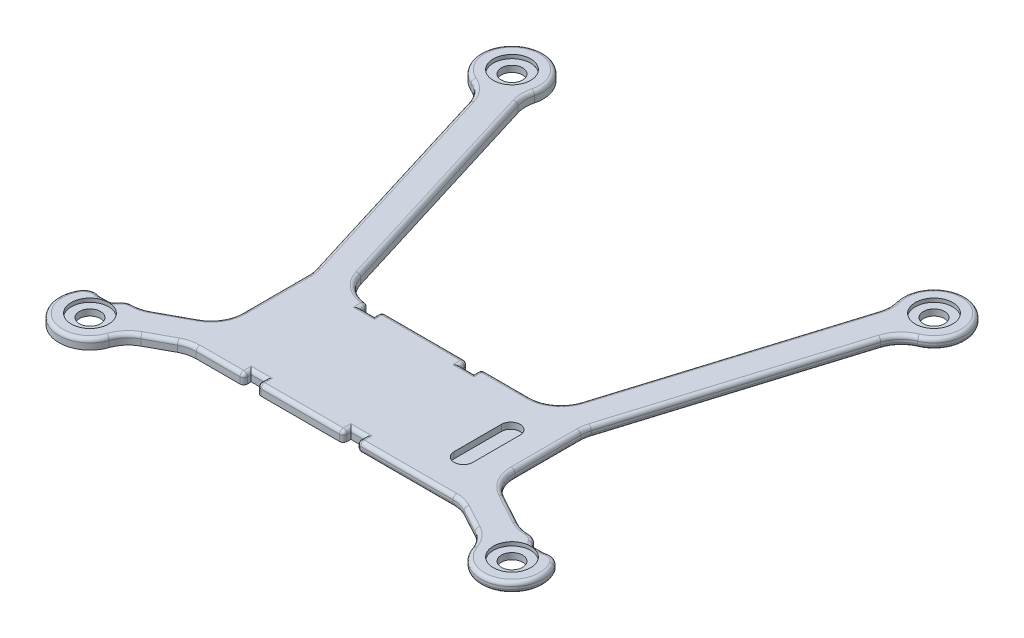
SolidWorks part; units mm, degrees
note: The reader was unsure of these and kept them because the rebuilt part matched: shared geometry of "草图1<4>".
material "PETG"
ref_plane "前视基准面" through (0, 0, 0) normal (0, 0, 1) x (1, 0, 0)
ref_plane "上视基准面" through (0, 0, 0) normal (0, 1, 0) x (1, 0, 0)
ref_plane "右视基准面" through (0, 0, 0) normal (1, 0, 0) x (0, 0, -1)
other "Configuration Table"
sketch "草图1" plane through (0, 0, 0) normal (0, 1, 0) x (1, 0, 0)
  line L0 (0, 38.1) -> (0, -38.1) construction
  line L1 (-33.9, -33.9) -> (33.9, -33.9) construction
  line L2 (-33.9, -33.9) -> (-33.9, 33.9) construction
  line L3 (-33.9, 33.9) -> (33.9, 33.9) construction
  line L4 (33.9, -33.9) -> (33.9, 33.9) construction
  line L5 (-33.9, -33.9) -> (33.9, 33.9) construction
  line L6 (-33.9, 33.9) -> (33.9, -33.9) construction
  line L7 (-21.9, -10.1) -> (21.9, -10.1)
  line L8 (-21.9, -10.1) -> (-21.9, -30.1)
  line L9 (-21.9, -30.1) -> (21.9, -30.1)
  line L10 (21.9, -10.1) -> (21.9, -30.1)
  line L11 (-21.9, -10.1) -> (21.9, -30.1) construction
  line L12 (-21.9, -30.1) -> (21.9, -10.1) construction
  line L13 (-38.1, 38.1) -> (38.1, 38.1) construction
  line L14 (-38.1, 38.1) -> (-38.1, -38.1) construction
  line L15 (-38.1, -38.1) -> (38.1, -38.1) construction
  line L16 (38.1, 38.1) -> (38.1, -38.1) construction
  line L17 (-38.1, 38.1) -> (38.1, -38.1) construction
  line L18 (-38.1, -38.1) -> (38.1, 38.1) construction
  line L19 (-21.9, -30.1) -> (-28.9, -33.9)
  line L20 (21.9, -30.1) -> (28.9, -33.9)
  line L21 (-31.4018, -29.5689) -> (-21.9, -24.4108)
  line L22 (31.4018, -29.5689) -> (21.9, -24.4108)
  line L23 (-33.9, 28.9) -> (-21.9, -10.1)
  line L24 (33.9, 28.9) -> (21.9, -10.1)
  line L25 (-29.485, 31.5531) -> (-16.6687, -10.1)
  line L26 (29.485, 31.5531) -> (16.6687, -10.1)
  circle A0 centre (-33.9, 33.9) radius 1.7
  circle A1 centre (33.9, 33.9) radius 1.7
  circle A2 centre (-33.9, -33.9) radius 1.7
  circle A3 centre (33.9, -33.9) radius 1.7
  circle A4 centre (-33.9, 33.9) radius 5
  circle A5 centre (33.9, 33.9) radius 5
  circle A6 centre (33.9, -33.9) radius 5
  circle A7 centre (-33.9, -33.9) radius 5
  circle A8 centre (-33.9, 33.9) radius 3
  circle A9 centre (33.9, 33.9) radius 3
  circle A10 centre (33.9, -33.9) radius 3
  circle A11 centre (-33.9, -33.9) radius 3
  point P0 (0, 0)
  point P14 (0, -20.1)
  point P19 (0, 0)
  dimension "D2" = 3.4
  dimension "D3" = 10
  dimension "D10" = 6
  dimension "D1" = 67.8
  dimension "D4" = 5
  dimension "D5" = 20
  dimension "D6" = 76.2
  dimension "D7" = 8
  dimension "D8" = 12
  dimension "D9" = 5
extrude "凸台-拉伸1" add sketch "草图1" along normal blind 1.6 contours A4 L23 L7 L25 | A5 L26 L7 L24 | L10 L7 L8 L9 | A6 L22 L10 L20 | A6 A10 | A10 A3 | A5 A9 | A9 A1 | A7 A11 | A7 L19 L8 L21 | A11 A2 | A4 A8 | A8 A0
extrude "切除-拉伸1" cut sketch "草图1<4>" against normal blind 0.6 from surface at 1.6 contours A8 A0 | A11 A2 | A10 A3 | A9 A1 starting at face at (0, 1.6, 9.3042)
sketch "草图1<4>" plane through (0, 0, 0) normal (0, 1, 0) x (1, 0, 0) same geometry as "草图1"
sketch "草图2" plane through (0, 1.6, 0) normal (0, 1, 0) x (1, 0, 0)
  line L0 (0, 0) -> (0, -30.1) construction
  line L2 (-33.9, -33.9) -> (-33.9, 33.9) construction
  line L3 (-21.9, -30.1) -> (21.9, -30.1) construction
  line L4 (-34.95, -33.9) -> (-34.95, -22.25) construction
  line L5 (36.6, -30.5) -> (33.3, -14) construction
  line L7 (-35.6, -14) -> (-34.3, -14)
  line L8 (-36.6, -15) -> (-36.6, -29.5)
  line L9 (-35.6, -30.5) -> (-34.3, -30.5)
  line L10 (-33.3, -15) -> (-33.3, -29.5)
  line L11 (-36.6, -14) -> (-33.3, -30.5) construction
  line L12 (-36.6, -30.5) -> (-33.3, -14) construction
  line L13 (36.6, -14) -> (33.3, -30.5) construction
  line L14 (34.95, -33.9) -> (34.95, -22.25) construction
  line L18 (33.3, -15) -> (33.3, -29.5)
  line L19 (35.6, -30.5) -> (34.3, -30.5)
  line L20 (36.6, -15) -> (36.6, -29.5)
  line L21 (35.6, -14) -> (34.3, -14)
  line L22 (-11.9, -10.1) -> (-11.9, -30.1) construction
  line L23 (-16.6687, -10.1) -> (16.6687, -10.1) construction
  line L24 (4.1, -10.1) -> (4.1, -30.1) construction
  line L25 (-11.9, -20.1) -> (4.1, -20.1) construction
  line L26 (-21.9, -10.1) -> (-21.9, -24.4108) construction
  line L27 (-13, -31.3) -> (-10.8, -31.3)
  line L28 (-13, -11.3) -> (-10.8, -11.3)
  line L29 (-13, -11.3) -> (-13, -8.9)
  line L30 (-13, -8.9) -> (-10.8, -8.9)
  line L31 (-10.8, -11.3) -> (-10.8, -8.9)
  line L32 (-13, -11.3) -> (-10.8, -8.9) construction
  line L33 (-13, -8.9) -> (-10.8, -11.3) construction
  line L34 (3, -11.3) -> (5.2, -11.3)
  line L35 (3, -11.3) -> (3, -8.9)
  line L36 (3, -8.9) -> (5.2, -8.9)
  line L37 (5.2, -11.3) -> (5.2, -8.9)
  line L38 (3, -11.3) -> (5.2, -8.9) construction
  line L39 (3, -8.9) -> (5.2, -11.3) construction
  line L40 (-10.8, -28.9) -> (-10.8, -31.3)
  line L41 (-13, -28.9) -> (-10.8, -28.9)
  line L42 (-13, -28.9) -> (-13, -31.3)
  line L43 (3, -31.3) -> (5.2, -31.3)
  line L44 (5.2, -28.9) -> (5.2, -31.3)
  line L45 (3, -28.9) -> (5.2, -28.9)
  line L46 (3, -28.9) -> (3, -31.3)
  arc A0 (-34.3, -30.5) -> (-33.3, -29.5) centre (-34.3, -29.5) ccw
  arc A1 (-36.6, -29.5) -> (-35.6, -30.5) centre (-35.6, -29.5) ccw
  arc A2 (-35.6, -14) -> (-36.6, -15) centre (-35.6, -15) ccw
  arc A3 (-34.3, -14) -> (-33.3, -15) centre (-34.3, -15) cw
  arc A4 (34.3, -14) -> (33.3, -15) centre (34.3, -15) ccw
  arc A5 (35.6, -14) -> (36.6, -15) centre (35.6, -15) cw
  arc A6 (36.6, -29.5) -> (35.6, -30.5) centre (35.6, -29.5) cw
  arc A7 (34.3, -30.5) -> (33.3, -29.5) centre (34.3, -29.5) cw
  dimension "D3" = 1
  dimension "D1" = 1.05
  dimension "D2" = 3.3
  dimension "D4" = 3.4
  dimension "D5" = 16.5
  dimension "D6" = 10
  dimension "D7" = 16
  dimension "D8" = 2.2
  dimension "D9" = 1.2
extrude "切除-拉伸2" cut sketch "草图2" against normal through all
fillet "圆角1" radius 5 16 edges at (-16.6687, 0.8, 10.1) (16.6687, 0.8, 10.1) (29.485, 0.8, -31.5531) (33.9, 0.8, -28.9) (21.9, 0.8, 10.1) (21.9, 0.8, 24.4108) (31.4018, 0.8, 29.5689) (28.9, 0.8, 33.9) (21.9, 0.8, 30.1) (-31.4018, 0.8, 29.5689) (-21.9, 0.8, 24.4108) (-21.9, 0.8, 10.1) (-33.9, 0.8, -28.9) (-29.485, 0.8, -31.5531) (-21.9, 0.8, 30.1) (-28.9, 0.8, 33.9)
fillet "圆角2" radius 2 4 edges at (-33.3, 0.8, 28.9361) (36.5835, 0.8, 29.6811) (-36.5835, 0.8, 29.6811) (33.3, 0.8, 28.9361)
fillet "圆角3" radius 0.6 8 edges at (5.2, 0.8, 10.1) (3, 0.8, 10.1) (-13, 0.8, 10.1) (-10.8, 0.8, 10.1) (5.2, 0.8, 30.1) (3, 0.8, 30.1) (-10.8, 0.8, 30.1) (-13, 0.8, 30.1)
sketch "草图4" plane through (0, 1.6, 0) normal (0, 1, 0) x (1, 0, 0)
  line L0 (16.1, -16.3) -> (16.1, -23.9) construction
  line L1 (17.6, -16.3) -> (17.6, -23.9)
  line L2 (14.6, -16.3) -> (14.6, -23.9)
  line L3 (-21.9, -10.8518) -> (-21.9, -21.4358) construction
  line L4 (-21.9, -20.1) -> (21.9, -20.1) construction
  line L5 (21.9, -10.8518) -> (21.9, -21.4358) construction
  line L6 (-10.2, -10.1) -> (2.4, -10.1) construction
  line L7 (-10.2, -30.1) -> (2.4, -30.1) construction
  arc A0 (17.6, -16.3) -> (14.6, -16.3) centre (16.1, -16.3) ccw
  arc A1 (14.6, -23.9) -> (17.6, -23.9) centre (16.1, -23.9) ccw
  point P2 (16.1, -20.1)
  point P18 (16.1, -25.4)
  dimension "D1" = 1.5
  dimension "D2" = 38
  dimension "D3" = 10.6
extrude "切除-拉伸3" cut sketch "草图4" against normal blind 1
fillet "圆角4" radius 0.6 91 edges at (5.2, 0, 29.2) (5.2, 1.6, 29.2) (5.3757, 1.6, 29.9243) (5.3757, 0, 29.9243) (13.2152, 1.6, 30.1) (13.2152, 0, 30.1) (21.8609, 1.6, 30.2538) (21.8609, 0, 30.2538) (24.9262, 0, 31.7428) (24.9262, 1.6, 31.7428) (28.2641, 1.6, 33.9397) (28.2641, 0, 33.9397) (5.2, 1.6, 11) (5.2, 0, 11) (5.3757, 1.6, 10.2757) (5.3757, 0, 10.2757) (9.3879, 0, 10.1) (9.3879, 1.6, 10.1) (15.9463, 1.6, 9.1219) (15.9463, 0, 9.1219) (23.3731, 0, -11.6893) (23.3731, 1.6, -11.6893) (29.2111, 1.6, -31.2999) (29.2111, 0, -31.2999) (36.1084, 0, -38.3859) (36.1084, 1.6, -38.3859) (34.123, 1.6, -28.0517) (34.123, 0, -28.0517) (27.5921, 0, -8.3994) (27.5921, 1.6, -8.3994) (21.9556, 1.6, 10.1084) (21.9556, 0, 10.1084) (21.9, 0, 16.1438) (21.9, 1.6, 16.1438) (22.6031, 1.6, 23.9925) (22.6031, 0, 23.9925) (26.9825, 0, 27.1698) (26.9825, 1.6, 27.1698) (30.5832, 1.6, 28.9559) (30.5832, 0, 28.9559) (32.7407, 1.6, 29.3654) (32.7407, 0, 29.3654) (33.8196, 0, 30.377) (33.8196, 1.6, 30.377) (34.95, 1.6, 30.5) (34.95, 0, 30.5) (35.7482, 1.6, 30.489) (35.7482, 0, 30.489) (37.2003, 0, 30.5026) (37.2003, 1.6, 30.5026) (-10.8, 1.6, 29.2) (-10.6243, 1.6, 29.9243) (3, 1.6, 29.2) (2.8243, 1.6, 29.9243) (-10.8, 1.6, 11) (-10.6243, 1.6, 10.2757) (3, 1.6, 11) (2.8243, 1.6, 10.2757) (-13, 1.6, 10.9826) (-13.1527, 1.6, 10.2652) (-16.1662, 1.6, 8.9499) (-23.3731, 1.6, -11.6893) (-29.2111, 1.6, -31.2999) (-36.1084, 1.6, -38.3859) (-34.123, 1.6, -28.0517) (-27.5921, 1.6, -8.3994) (-21.9556, 1.6, 10.1084) (-21.9, 1.6, 16.1438) (-22.6031, 1.6, 23.9925) (-26.9825, 1.6, 27.1698) (-30.5832, 1.6, 28.9559) (-32.7407, 1.6, 29.3654) (-33.8196, 1.6, 30.377) (-34.95, 1.6, 30.5) (-35.7482, 1.6, 30.489) (-37.2003, 1.6, 30.5026) (-13, 1.6, 29.2) (-13.1757, 1.6, 29.9243) (-17.1152, 1.6, 30.1) (-21.8609, 1.6, 30.2538) (-24.9262, 1.6, 31.7428) (-28.2641, 1.6, 33.9397) (36.0058, 0, 38.4349) (36.0058, 1.6, 38.4349) (4.1, 1.6, 11.3) (-11.9, 1.6, 11.3) (4.1, 1.6, 28.9) (-11.9, 1.6, 28.9) (-3.9, 1.6, 30.1) (-3.9, 1.6, 10.1) (-36.0058, 1.6, 38.4349)
